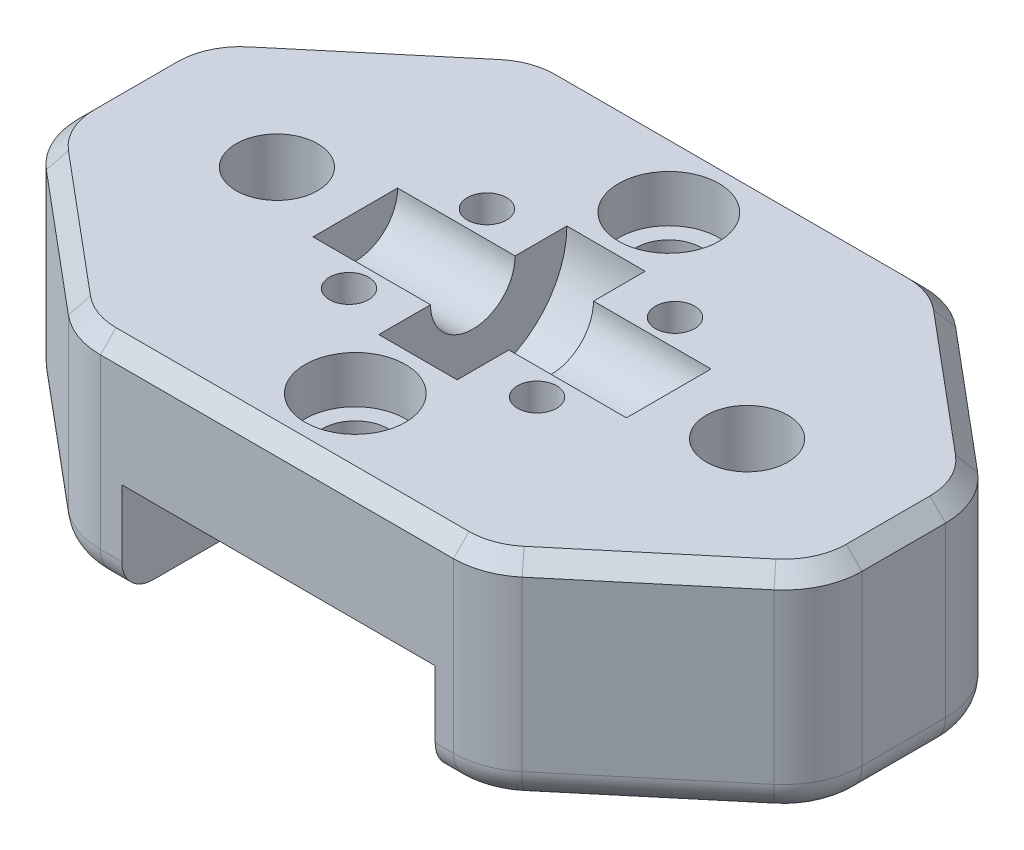
SolidWorks part; units mm, degrees
ref_plane "Front Plane" through (0, 0, 0) normal (0, 0, 1) x (1, 0, 0)
ref_plane "Top Plane" through (0, 0, 0) normal (0, 1, 0) x (1, 0, 0)
ref_plane "Right Plane" through (0, 0, 0) normal (1, 0, 0) x (0, 0, -1)
sketch "Sketch1" plane through (0, 0, 0) normal (0, 1, 0) x (1, 0, 0)
  line L0 (14.3035, 0) -> (-14.3035, 0)
  line L1 (-18.3852, 1.4856) -> (-29.4817, 10.7967)
  line L2 (-31.75, 15.6611) -> (-31.75, 22.4389)
  line L3 (-31.75, 19.05) -> (0, 19.05) construction
  line L4 (0, 19.05) -> (0, 0) construction
  line L5 (18.3852, 1.4856) -> (29.4817, 10.7967)
  line L6 (31.75, 15.6611) -> (31.75, 22.4389)
  line L7 (-18.3852, 36.6144) -> (-29.4817, 27.3033)
  line L8 (14.3035, 38.1) -> (-14.3035, 38.1)
  line L9 (18.3852, 36.6144) -> (29.4817, 27.3033)
  arc A0 (-29.4817, 10.7967) -> (-31.75, 15.6611) centre (-25.4, 15.6611) cw
  arc A1 (-18.3852, 1.4856) -> (-14.3035, 0) centre (-14.3035, 6.35) ccw
  arc A2 (18.3852, 1.4856) -> (14.3035, 0) centre (14.3035, 6.35) cw
  arc A3 (29.4817, 10.7967) -> (31.75, 15.6611) centre (25.4, 15.6611) ccw
  arc A4 (-29.4817, 27.3033) -> (-31.75, 22.4389) centre (-25.4, 22.4389) ccw
  arc A5 (-18.3852, 36.6144) -> (-14.3035, 38.1) centre (-14.3035, 31.75) cw
  arc A6 (18.3852, 36.6144) -> (14.3035, 38.1) centre (14.3035, 31.75) ccw
  arc A7 (29.4817, 27.3033) -> (31.75, 22.4389) centre (25.4, 22.4389) cw
  point P9 (-31.75, 12.7)
  point P31 (31.75, 19.05)
  dimension "D5" = 6.35
  dimension "D6" = 6.35
  dimension "D1" = 19.05
  dimension "D2" = 6.35
  dimension "D3" = 31.75
  dimension "D4" = 140
extrude "Boss-Extrude2" add sketch "Sketch1" along normal blind 17.4625
sketch "Sketch2" plane through (0, 17.4625, 0) normal (0, 1, 0) x (1, 0, 0)
  line L0 (-14.3035, 0) -> (14.3035, 0) construction
  line L2 (14.3035, 38.1) -> (-14.3035, 38.1) construction
  line L3 (0, 38.1) -> (0, 0) construction
  circle A0 centre (-19.05, 19.05) radius 3.302
  circle A3 centre (19.05, 19.05) radius 3.302
  circle A8 centre (7.62, 24.638) radius 1.5875
  circle A9 centre (7.62, 13.462) radius 1.5875
  circle A10 centre (-7.62, 13.462) radius 1.5875
  circle A11 centre (-7.62, 24.638) radius 1.5875
  circle A12 centre (0, 31.75) radius 2.667
  circle A13 centre (0, 6.35) radius 2.667
  point P4 (0, 0)
  dimension "D2" = 6.604
  dimension "D7" = 7.62
  dimension "D8" = 3.175
  dimension "D10" = 5.588
  dimension "D4" = 5.334
  dimension "D1" = 19.05
  dimension "D3" = 19.05
  dimension "D5" = 6.35
  dimension "D6" = 6.35
  dimension "D9" = 5.588
  dimension "D11" = 7.62
  dimension "D12" = 25.4
extrude "Cut-Extrude1" cut sketch "Sketch2" against normal through all
sketch "Sketch3" plane through (-31.75, 0, 0) normal (-1, 0, 0) x (0, 0, 1)
  line L0 (-22.4389, 17.4625) -> (-15.6611, 17.4625) construction
  circle A0 centre (-19.05, 17.4625) radius 3.429
  dimension "D1" = 6.858
extrude "Cut-Extrude3" cut sketch "Sketch3" against normal blind 25.4 from offset 19.05 offset against normal yes
sketch "Sketch4" plane through (-31.75, 0, 0) normal (-1, 0, 0) x (0, 0, 1)
  line L0 (-22.4389, 17.4625) -> (-15.6611, 17.4625) construction
  line L1 (-26.67, 17.4625) -> (-11.43, 17.4625)
  arc A0 (-26.67, 17.4625) -> (-11.43, 17.4625) centre (-19.05, 17.4625) ccw
  dimension "D1" = 7.62
extrude "Cut-Extrude4" cut sketch "Sketch4" against normal blind 6.35 from offset 28.575 offset against normal yes
sketch "Sketch5" plane through (0, 0, -38.1) normal (0, 0, -1) x (-1, 0, 0)
  line L0 (-14.3035, 0) -> (14.3035, 0) construction
  line L1 (12.573, 0) -> (-12.827, 0)
  line L2 (12.573, 0) -> (12.573, 7.9375)
  line L3 (12.573, 7.9375) -> (-12.827, 7.9375)
  line L4 (-12.827, 0) -> (-12.827, 7.9375)
  line L5 (-14.3035, 17.4625) -> (14.3035, 17.4625) construction
  point P10 (0, 17.4625)
  dimension "D1" = 25.4
  dimension "D2" = 7.9375
  dimension "D3" = 12.827
extrude "Cut-Extrude5" cut sketch "Sketch5" against normal through all
sketch "Sketch6" plane through (0, 0, 0) normal (0, -1, 0) x (1, 0, 0)
  line L1 (13.208, -22.4229) -> (19.05, -25.7958)
  line L2 (19.05, -25.7958) -> (24.892, -22.4229)
  line L3 (24.892, -22.4229) -> (24.892, -15.6771)
  line L4 (24.892, -15.6771) -> (19.05, -12.3042)
  line L5 (19.05, -12.3042) -> (13.208, -15.6771)
  line L6 (13.208, -15.6771) -> (13.208, -22.4229)
  line L7 (-19.05, -25.7958) -> (-13.208, -22.4229)
  line L8 (-13.208, -22.4229) -> (-13.208, -15.6771)
  line L9 (-13.208, -15.6771) -> (-19.05, -12.3042)
  line L10 (-19.05, -12.3042) -> (-24.892, -15.6771)
  line L11 (-24.892, -15.6771) -> (-24.892, -22.4229)
  line L12 (-24.892, -22.4229) -> (-19.05, -25.7958)
  circle A0 centre (19.05, -19.05) radius 5.842 construction
  circle A1 centre (-19.05, -19.05) radius 5.842 construction
  dimension "D1" = 11.684
extrude "Cut-Extrude6" cut sketch "Sketch6" against normal blind 7.9375
sketch "Sketch9" plane through (0, 7.9375, 0) normal (0, -1, 0) x (1, 0, 0)
  line L0 (9.2075, -13.462) -> (9.2075, -24.638)
  line L1 (6.0325, -13.462) -> (6.0325, -24.638)
  line L2 (-6.0325, -24.638) -> (-6.0325, -13.462)
  line L3 (-9.2075, -24.638) -> (-9.2075, -13.462)
  circle A0 centre (7.62, -13.462) radius 1.5875 construction
  circle A1 centre (7.62, -24.638) radius 1.5875 construction
  circle A2 centre (-7.62, -24.638) radius 1.5875 construction
  circle A3 centre (-7.62, -13.462) radius 1.5875 construction
  arc A4 (9.2075, -24.638) -> (6.0325, -24.638) centre (7.62, -24.638) cw
  arc A5 (-6.0325, -24.638) -> (-9.2075, -24.638) centre (-7.62, -24.638) cw
  arc A6 (-9.2075, -13.462) -> (-6.0325, -13.462) centre (-7.62, -13.462) cw
  arc A7 (6.0325, -13.462) -> (9.2075, -13.462) centre (7.62, -13.462) cw
extrude "Cut-Extrude9" cut sketch "Sketch9" against normal blind 3.175
chamfer "Chamfer2" distance 2.54 angle 45 4 edges at (-7.62, 11.1125, -15.0495) (-7.62, 11.1125, -23.0505) (7.62, 11.1125, -15.0495) (7.62, 11.1125, -23.0505)
sketch "Sketch10" plane through (0, 17.4625, 0) normal (0, 1, 0) x (1, 0, 0)
  circle A0 centre (0, 6.35) radius 4.064
  circle A1 centre (0, 31.7584) radius 4.064
  dimension "D1" = 8.128
extrude "Cut-Extrude10" cut sketch "Sketch10" against normal blind 3.81
fillet "Fillet1" radius 2.54 18 edges at (-31.1551, 0, -25.1226) (-31.75, 0, -19.05) (-31.1551, 0, -12.9774) (-23.9335, 0, -6.1411) (-16.4753, 0, -0.383) (-13.4383, 0, 0) (-23.9335, 0, -31.9589) (-16.4753, 0, -37.717) (-13.4383, 0, -38.1) (13.5653, 0, 0) (16.4753, 0, -0.383) (23.9335, 0, -6.1411) (31.1551, 0, -12.9774) (31.75, 0, -19.05) (31.1551, 0, -25.1226) (23.9335, 0, -31.9589) (16.4753, 0, -37.717) (13.5653, 0, -38.1)
fillet "Fillet2" radius 1.27 8 edges at (-7.62, 7.9375, -26.2255) (-9.2075, 7.9375, -19.05) (-7.62, 7.9375, -11.8745) (-6.0325, 7.9375, -19.05) (7.62, 7.9375, -11.8745) (9.2075, 7.9375, -19.05) (7.62, 7.9375, -26.2255) (6.0325, 7.9375, -19.05)
chamfer "Chamfer3" distance 1.27 angle 45 16 edges at (16.4753, 17.4625, -37.717) (0, 17.4625, -38.1) (-16.4753, 17.4625, -37.717) (-23.9335, 17.4625, -31.9589) (-31.1551, 17.4625, -25.1226) (-31.75, 17.4625, -19.05) (-31.1551, 17.4625, -12.9774) (-23.9335, 17.4625, -6.1411) (-16.4753, 17.4625, -0.383) (0, 17.4625, 0) (16.4753, 17.4625, -0.383) (23.9335, 17.4625, -6.1411) (31.1551, 17.4625, -12.9774) (31.75, 17.4625, -19.05) (31.1551, 17.4625, -25.1226) (23.9335, 17.4625, -31.9589)
